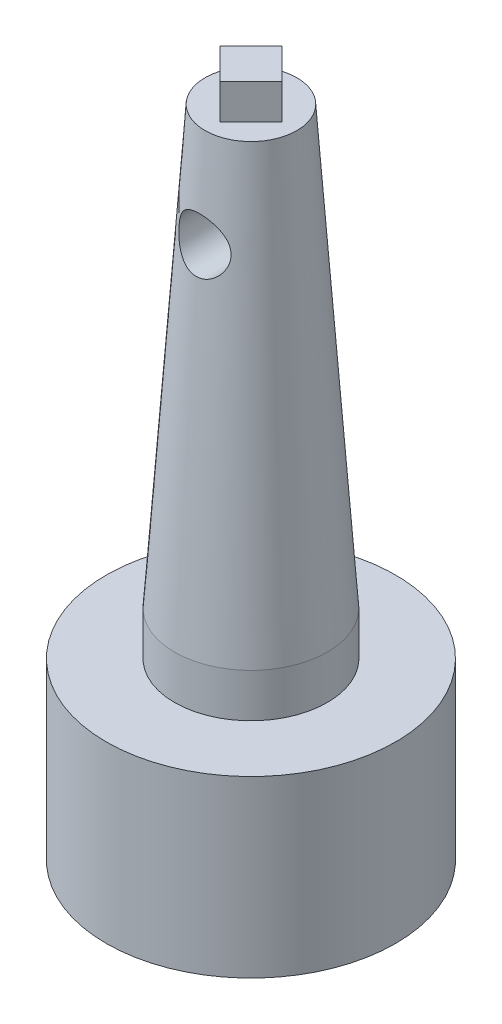
SolidWorks part; units mm, degrees
ref_plane "Front Plane" through (0, 0, 0) normal (0, 0, 1) x (1, 0, 0)
ref_plane "Top Plane" through (0, 0, 0) normal (0, 1, 0) x (1, 0, 0)
ref_plane "Right Plane" through (0, 0, 0) normal (1, 0, 0) x (0, 0, -1)
sketch "Sketch1" plane through (0, 0, 0) normal (0, 1, 0) x (1, 0, 0)
  circle A0 centre (0, 0) radius 33.14
  dimension "D1" = 66.28
sketch "Sketch2" plane through (0, 0, 0) normal (0, 0, 1) x (1, 0, 0)
  line L2 (0, 33.14) -> (0, 0)
  line L3 (0, 0) -> (33.14, 0)
  arc A0 (33.14, 0) -> (0, 33.14) centre (0, 0) ccw
sketch "Sketch3" plane through (0, 0, 0) normal (0, 0, 1) x (1, 0, 0)
  line L0 (0, 0) -> (0, 250)
ref_plane "Plane1" through (0, 250, 0) normal (0, 1, 0) x (1, 0, 0)
extrude "Boss-Extrude7" add sketch "Sketch1" along normal blind 40
revolve "Cut-Revolve1" cut sketch "Sketch2" angle 360 about L2
sketch "Sketch4" plane through (0, 40, 0) normal (0, 1, 0) x (1, 0, 0)
  circle A0 centre (0, 0) radius 17.5
  dimension "D1" = 35
extrude "Cut-Extrude1" cut sketch "Sketch4" against normal blind 5
ref_plane "Plane2" through (0, 50, 0) normal (0, 1, 0) x (1, 0, 0)
sketch "Sketch5" plane through (0, 50, 0) normal (0, 1, 0) x (1, 0, 0)
  circle A0 centre (0, 0) radius 17.5 construction
  circle A1 centre (0, 0) radius 17.5
extrude "Boss-Extrude8" add sketch "Sketch5" along normal blind 100 draft 4 and the other way up to next (15 mm away)
sketch "Sketch6" plane through (0, 150, 0) normal (0, 1, 0) x (1, 0, 0)
  line L0 (0, 7.07) -> (-7.0721, 0)
  line L1 (-7.0721, 0) -> (0, -7.07)
  line L2 (0, -7.07) -> (7.0721, 0)
  line L3 (7.0721, 0) -> (0, 7.07)
  line L4 (0, 10.5073) -> (0, -10.5073) construction
  circle A1 centre (0, 0) radius 10.5073 construction
  dimension "D1" = 10
  dimension "D2" = 7.07
extrude "Boss-Extrude9" add sketch "Sketch6" along normal blind 8
sketch "Sketch7" plane through (-0.2939, 0, 39.9989) normal (-0.0073, 0, 1) x (1, 0, 0.0073)
  circle A0 centre (0, 128) radius 6
extrude "Cut-Extrude2" cut sketch "Sketch7" against normal through all
